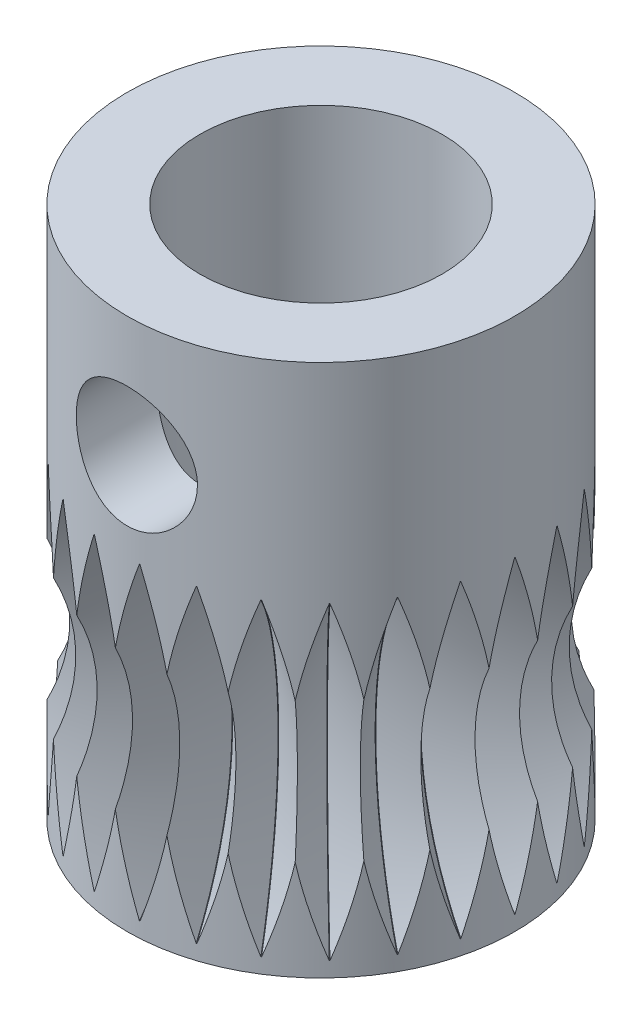
SolidWorks part; units mm, degrees
ref_plane "Front Plane" through (0, 0, 0) normal (0, 0, 1) x (1, 0, 0)
ref_plane "Top Plane" through (0, 0, 0) normal (0, 1, 0) x (1, 0, 0)
ref_plane "Right Plane" through (0, 0, 0) normal (1, 0, 0) x (0, 0, -1)
sketch "Sketch1" plane through (0, 0, 0) normal (0, 1, 0) x (1, 0, 0)
  circle A0 centre (0, 0) radius 4
  circle A1 centre (0, 0) radius 2.5
  dimension "D1" = 8
  dimension "D2" = 5
extrude "Boss-Extrude1" add sketch "Sketch1" along normal blind 11
ref_plane "Plane1" through (0, 0, 4) normal (0, 0, 1) x (1, 0, 0)
ref_axis "Axis1" through (0, 11, 0) along (0, -1, 0)
hole_wizard "M3 Tapped Hole1" positions "Sketch6" profile "Sketch7" tap size "M3" standard "ISO" end condition up to next
sketch "Sketch6" plane through (0, 0, 4) normal (0, 0, 1) x (1, 0, 0)
  line L0 (4, 11) -> (-4, 11) construction
  line L1 (0, 11) -> (0, 0) construction
  point P1 (0, 8.5)
  dimension "D1" = 2.5
cosmetic thread "Hole Thread1" parameters "D2"=3
sketch "Sketch7" plane through (0, 8.5, 4) normal (1, 0, 0) x (0, -1, 0)
  line L0 (0, 0) -> (0, 1.5)
  line L1 (0, 1.5) -> (1.25, 1.5)
  line L2 (1.25, 1.5) -> (1.25, 0)
  line L5 (1.25, 0) -> (0, 0)
  line L11 (0, -6.35) -> (0, 107.95) construction
  dimension "Thru Tap Drill Dia." = 2.5
  dimension "Thru Tap Drill Depth" = 1.5
ref_plane "Plane3" through (0, 0, 0) normal (0, 0, 1) x (1, 0, 0)
sketch "Sketch8" plane through (0, 0, 0) normal (0, 0, 1) x (1, 0, 0)
  line L0 (0, 11) -> (0, 0) construction
  line L1 (4, 11) -> (-4, 11) construction
  line L2 (7.85, 3.5) -> (7.85, 8.3641) construction
  circle A0 centre (7.85, 3.5) radius 5
  point P6 (7.85, 8.5)
  dimension "D1" = 10
  dimension "D2" = 7.85
  dimension "D3" = 7.5
ref_plane "Plane4" through (7.85, 0, 0) normal (1, 0, 0) x (0, 0, -1)
sketch "Sketch10" plane through (7.85, 0, 0) normal (1, 0, 0) x (0, 0, -1)
  line L0 (-1.6192, 5.7042) -> (1.6192, 5.7042)
  line L1 (1.6192, 5.7042) -> (0.005, 8.5)
  line L2 (0.005, 8.5) -> (-0.005, 8.5)
  line L3 (-0.005, 8.5) -> (-1.6192, 5.7042)
  line L6 (0, 3.5) -> (0, 8.3641) construction
  point P2 (0, 8.5)
  point P5 (0, 5.7042)
  dimension "D1" = 0.01
  dimension "D2" = 60
sweep "Cut-Sweep1" cut profiles "Sketch10" path "Sketch8"
pattern_circular "CirPattern1" count 25 over 360 about axis through (0, 11, 0) along (0, -1, 0) of "Cut-Sweep1"
